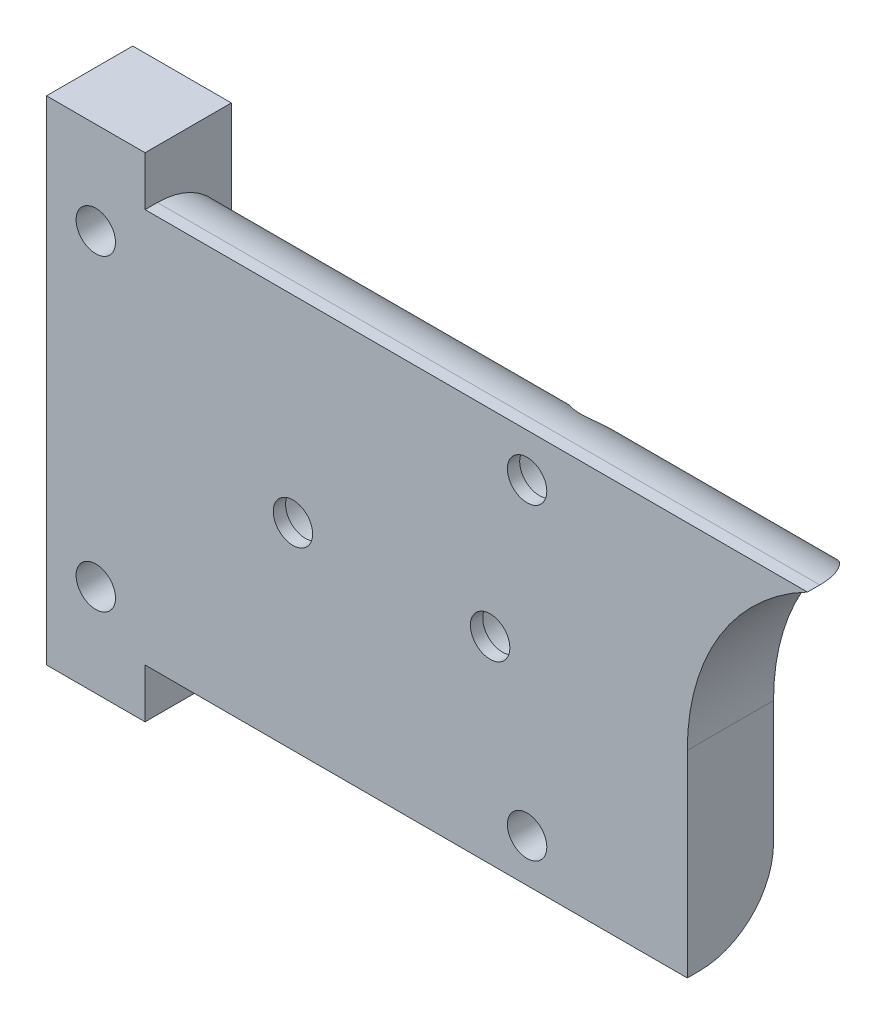
SolidWorks part; units mm, degrees
ref_plane "Front Plane" through (0, 0, 0) normal (0, 0, 1) x (1, 0, 0)
ref_plane "Top Plane" through (0, 0, 0) normal (0, 1, 0) x (1, 0, 0)
ref_plane "Right Plane" through (0, 0, 0) normal (1, 0, 0) x (0, 0, -1)
sketch "Sketch1" plane through (0, 0, 0) normal (0, 0, 1) x (1, 0, 0)
  line L0 (45.1613, 0) -> (10.1613, 0) construction
  line L1 (10.1613, 0) -> (10.1613, -8)
  line L2 (10.1613, 8) -> (10.1613, 0)
  line L3 (10.1613, 8) -> (41.0382, 8)
  line L4 (10.1613, -8) -> (41.0382, -8)
  line L5 (36.1613, 0) -> (36.1613, -8)
  line L6 (10.1613, 8) -> (10.1613, 10)
  line L7 (10.1613, 10) -> (14.1613, 10)
  line L8 (14.1613, 10) -> (14.1613, 8)
  line L9 (10.1613, -8) -> (10.1613, -10)
  line L10 (10.1613, -10) -> (14.1613, -10)
  line L11 (14.1613, -10) -> (14.1613, -8)
  circle A0 centre (45.1613, 0) radius 9
extrude "Boss-Extrude1" add sketch "Sketch1" along normal blind 3.5 contours L0 A0 L2 | L0 L1 | L8 L7 L6 L3 | L10 L11 L4 L9 region at (23.1613, -4, 0) region at (23.8925, 4.1082, 0) region at (12.1613, -9, 0) region at (12.1613, 9, 0)
sketch "Sketch2" plane through (0, 0, 0) normal (0, 0, 1) x (1, 0, 0)
  line L0 (10.1613, 0) -> (12.1613, 0) construction
  line L1 (12.1613, 0) -> (12.1613, 6.25) construction
  line L2 (10.1613, 0) -> (20.1613, 0) construction
  line L3 (12.1613, 0) -> (12.1613, -6.25) construction
  line L4 (12.1613, 0) -> (29.6613, 0) construction
  line L5 (29.6613, 0) -> (29.6613, 6.25) construction
  line L6 (29.6613, 0) -> (29.6613, -6.25) construction
  line L7 (10.1613, 8) -> (10.1613, 0) construction
  line L8 (20.1613, 0) -> (28.1613, 0) construction
  circle A0 centre (20.1613, 0) radius 0.8
  circle A1 centre (12.1613, -6.25) radius 0.8
  circle A2 centre (29.6613, 6.25) radius 0.8
  circle A3 centre (29.6613, -6.25) radius 0.8
  circle A4 centre (12.1613, 6.25) radius 0.8
  circle A5 centre (28.1613, 0) radius 0.8
extrude "Screw Holes" cut sketch "Sketch2" along normal through all
sketch "Sketch3" plane through (0, 0, 0) normal (0, 0, 1) x (1, 0, 0)
  circle A0 centre (20.1613, 0) radius 1.25
  circle A1 centre (29.6613, 6.25) radius 1.25
  circle A2 centre (28.1613, 0) radius 1.25
extrude "Screw Heads" cut sketch "Sketch3" along normal blind 3
fillet "Fillet1" radius 3 2 edges at (25.1613, -8, 0) (27.5997, 8, 0)
